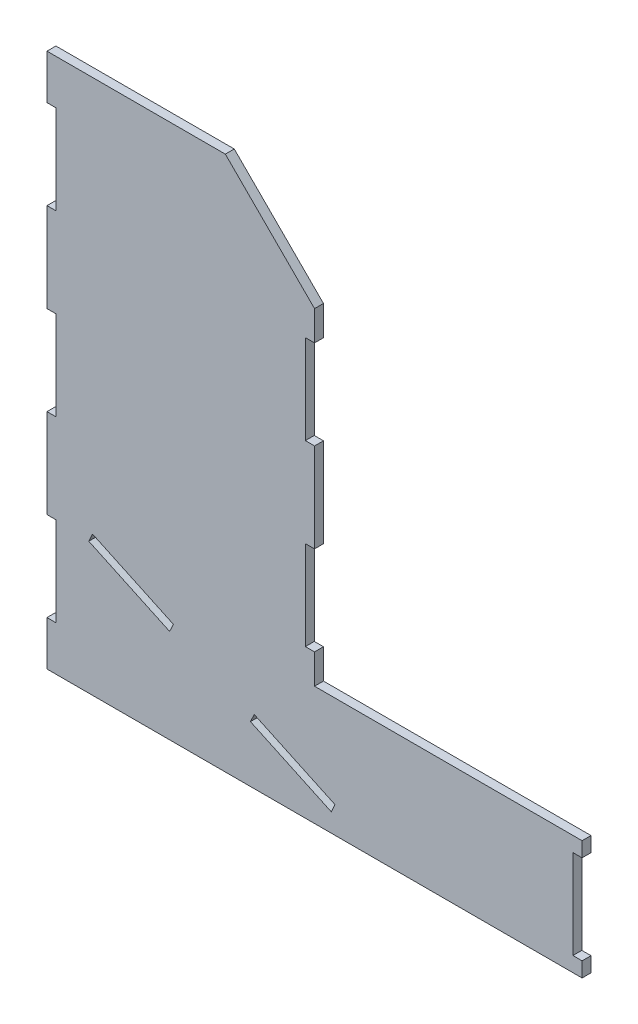
SolidWorks part; units mm, degrees
material "Maple"
ref_plane "Front Plane" through (0, 0, 0) normal (0, 0, 1) x (1, 0, 0)
ref_plane "Top Plane" through (0, 0, 0) normal (0, 1, 0) x (1, 0, 0)
ref_plane "Right Plane" through (0, 0, 0) normal (1, 0, 0) x (0, 0, -1)
sketch "Sketch1" plane through (0, 0, 0) normal (0, 0, 1) x (1, 0, 0)
  line L0 (-93.9149, 114.3977) -> (-93.9149, -65.6023)
  line L1 (-93.9149, -65.6023) -> (86.0851, -65.6023)
  line L2 (86.0851, -65.6023) -> (86.0851, -25.6023)
  line L3 (86.0851, -25.6023) -> (-3.9149, -25.6023)
  line L4 (-3.9149, -25.6023) -> (-3.9149, 84.3977)
  line L5 (-3.9149, 84.3977) -> (-33.9149, 114.3977)
  line L6 (-33.9149, 114.3977) -> (-93.9149, 114.3977)
  line L7 (-92.4149, 114.3977) -> (-92.4149, -65.6023) construction
  line L8 (-92.4149, 99.3977) -> (-92.4149, 69.3977)
  line L9 (-93.9149, 24.3977) -> (-3.9149, 24.3977) construction
  line L10 (-92.4149, 9.3977) -> (-92.4149, 39.3977)
  line L11 (-92.4149, -50.6023) -> (-92.4149, -20.6023)
  line L12 (86.0851, -45.6023) -> (-93.9149, -45.6023) construction
  line L13 (-5.4149, 84.3977) -> (-5.4149, -25.6023) construction
  line L14 (-5.4149, 74.3977) -> (-5.4149, 44.3977)
  line L15 (-5.4149, 29.3977) -> (-19.91, 29.3977) construction
  line L16 (-5.4149, -15.6023) -> (-5.4149, 14.3977)
  line L17 (84.5851, -25.6023) -> (84.5851, -65.6023) construction
  line L18 (84.5851, -30.6023) -> (84.5851, -60.6023)
  point P19 (-92.4149, 24.3977)
  dimension "D1" = 180
  dimension "D2" = 180
  dimension "D3" = 90
  dimension "D5" = 40
  dimension "D6" = 30
  dimension "D4" = 45
  dimension "D7" = 1.5
  dimension "D8" = 0
  dimension "D9" = 0
  dimension "D10" = 30
  dimension "D11" = 30
  dimension "D12" = 30
  dimension "D13" = 30
  dimension "D14" = 30
  dimension "D15" = 1.5
  dimension "D16" = 0
  dimension "D17" = 0
  dimension "D18" = 30
  dimension "D19" = 30
  dimension "D20" = 1.5
  dimension "D21" = 0
  dimension "D22" = 0
  dimension "D23" = 30
extrude "Boss-Extrude1" add sketch "Sketch1" along normal mid plane 3 contours L5 L6 L0 L1 L2 L3 L4 region at (-32.9847, 9.514, 0)
extrude "Cut-Extrude-Thin1" cut sketch "Sketch1<3>" against normal through all both and the other way through all thin contours L8 | L10 | L11 | L14 | L16 | L18 thin type mid plane wall 3.18
sketch "Sketch1<3>" plane through (0, 0, 0) normal (0, 0, 1) x (1, 0, 0) same geometry as "Sketch1"
fillet "Fillet2" [suppressed] radius 4
sketch "Sketch2" plane through (0, 0, 1.5) normal (0, 0, 1) x (1, 0, 0)
  line L1 (-25.4733, -46.6976) -> (1.7159, -59.3761) construction
  line L3 (1.7159, -59.3761) -> (2.9837, -56.6572) construction
  line L5 (2.9837, -56.6572) -> (-24.2055, -43.9786) construction
  line L7 (-24.2055, -43.9786) -> (-25.4733, -46.6976) construction
  line L21 (-51.3947, -31.3001) -> (-78.584, -18.6215) construction
  line L23 (-78.584, -18.6215) -> (-79.8518, -21.3405) construction
  line L25 (-79.8518, -21.3405) -> (-52.6626, -34.019) construction
  line L27 (-52.6626, -34.019) -> (-51.3947, -31.3001) construction
  line L40 (-25.4733, -46.6976) -> (1.7159, -59.3761)
  line L41 (1.7159, -59.3761) -> (2.9837, -56.6572)
  line L42 (2.9837, -56.6572) -> (-24.2055, -43.9786)
  line L43 (-24.2055, -43.9786) -> (-25.4733, -46.6976)
  line L44 (-51.3947, -31.3001) -> (-78.584, -18.6215)
  line L45 (-78.584, -18.6215) -> (-79.8518, -21.3405)
  line L46 (-79.8518, -21.3405) -> (-52.6626, -34.019)
  line L47 (-52.6626, -34.019) -> (-51.3947, -31.3001)
extrude "Cut-Extrude1" cut sketch "Sketch2" against normal up to next
equation "\"D7@Sketch1\"= \"lateral offset@tower.Assembly\""
equation "\"D8@Sketch1\" = \"vertical offset@tower.Assembly\""
equation "\"D9@Sketch1\"= \"vertical offset@tower.Assembly\""
equation "\"D12@Sketch1\"=\"D10@Sketch1\""
equation "\"D13@Sketch1\"=\"D10@Sketch1\""
equation "\"D11@Sketch1\"=\"D10@Sketch1\""
equation "\"D14@Sketch1\"=\"D10@Sketch1\""
equation "\"D1@Boss-Extrude1\" = \"T@tower.Assembly\""
equation "\"D15@Sketch1\"=\"D7@Sketch1\""
equation "\"D16@Sketch1\"=\"D8@Sketch1\""
equation "\"D17@Sketch1\"=\"D8@Sketch1\""
equation "\"D18@Sketch1\"=\"D10@Sketch1\""
equation "\"D19@Sketch1\"=\"D18@Sketch1\""
equation "\"D20@Sketch1\"=\"D7@Sketch1\""
equation "\"D21@Sketch1\"=\"D8@Sketch1\""
equation "\"D22@Sketch1\"=\"D8@Sketch1\""
equation "\"D23@Sketch1\"=\"D10@Sketch1\""
equation "\"D2@Sketch1\"=\"D3@Sketch1\"*2"
equation "\"D3@Sketch1\"=\"width@tower.Assembly\""
equation "\"D1@Sketch1\"=2*\"width@tower.Assembly\""
